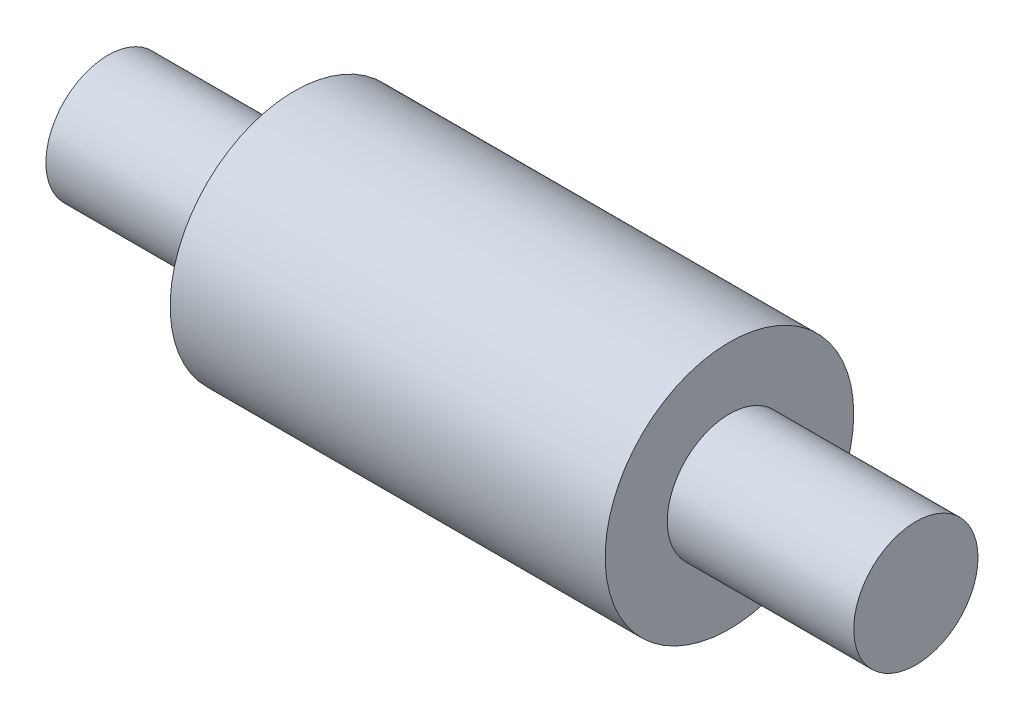
SolidWorks part; units mm, degrees
material "AISI 1015 Steel, Cold Drawn (SS)"
ref_plane "Front Plane" through (0, 0, 0) normal (0, 0, 1) x (1, 0, 0)
ref_plane "Top Plane" through (0, 0, 0) normal (0, 1, 0) x (1, 0, 0)
ref_plane "Right Plane" through (0, 0, 0) normal (1, 0, 0) x (0, 0, -1)
sketch "Sketch1" plane through (0, 0, 0) normal (0, 1, 0) x (1, 0, 0)
  line L0 (-65.2281, 0) -> (60.5547, 0) construction
  line L1 (0, 0) -> (0, 10)
  line L2 (0, 10) -> (30, 10)
  line L3 (30, 10) -> (30, 20)
  line L4 (30, 20) -> (100, 20)
  line L5 (100, 20) -> (100, 10)
  line L6 (100, 10) -> (130, 10)
  line L7 (130, 10) -> (130, 0)
  line L8 (130, 0) -> (0, 0)
revolve "Revolve1" add sketch "Sketch1" angle 360 about L8
